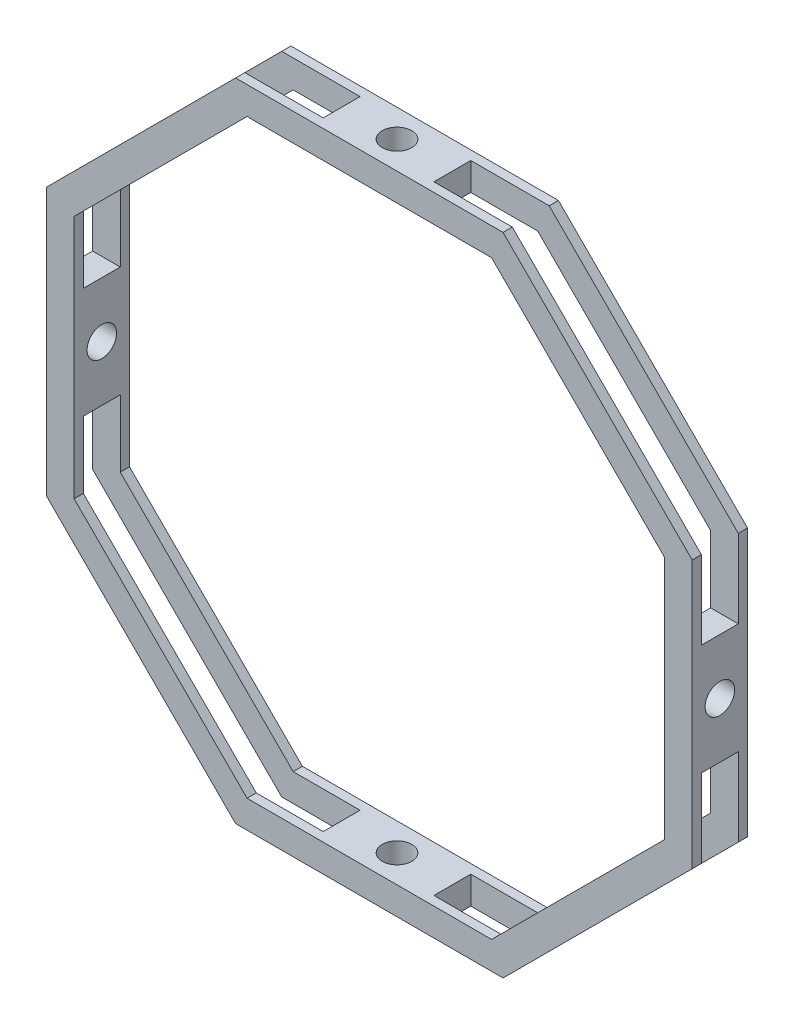
SolidWorks part; units mm, degrees
ref_plane "Plano frontal" through (0, 0, 0) normal (0, 0, 1) x (1, 0, 0)
ref_plane "Plano superior" through (0, 0, 0) normal (0, 1, 0) x (1, 0, 0)
ref_plane "Plano direito" through (0, 0, 0) normal (1, 0, 0) x (0, 0, -1)
sketch "Esboço1" plane through (0, 0, 0) normal (0, 0, 1) x (1, 0, 0)
  line L9 (175, 72.4874) -> (72.4874, 175)
  line L10 (72.4874, 175) -> (-72.4874, 175)
  line L11 (-72.4874, 175) -> (-175, 72.4874)
  line L12 (-175, 72.4874) -> (-175, -72.4874)
  line L13 (-175, -72.4874) -> (-72.4874, -175)
  line L14 (-72.4874, -175) -> (72.4874, -175)
  line L15 (72.4874, -175) -> (175, -72.4874)
  line L16 (175, -72.4874) -> (175, 72.4874)
  line L17 (160, 66.2742) -> (66.2742, 160)
  line L18 (66.2742, 160) -> (-66.2742, 160)
  line L19 (-66.2742, 160) -> (-160, 66.2742)
  line L20 (-160, 66.2742) -> (-160, -66.2742)
  line L21 (-160, -66.2742) -> (-66.2742, -160)
  line L22 (-66.2742, -160) -> (66.2742, -160)
  line L23 (66.2742, -160) -> (160, -66.2742)
  line L24 (160, -66.2742) -> (160, 66.2742)
  circle A0 centre (0, 0) radius 175 construction
  circle A1 centre (0, 0) radius 160 construction
extrude "Ressalto-extrusão1" add sketch "Esboço1" along normal blind 30
sketch "Esboço2" plane through (175, 0, 0) normal (1, 0, 0) x (0, 0, -1)
  line L0 (-30, 72.4874) -> (0, 72.4874) construction
  line L1 (-30, -72.4874) -> (-30, 72.4874) construction
  line L3 (0, 0) -> (0, 30)
  line L4 (0, 30) -> (-30, 30)
  line L5 (-30, 0) -> (-30, 30)
  line L6 (0, 30) -> (-5, 30)
  line L8 (0, 0) -> (0, -30)
  line L9 (0, -30) -> (-30, -30)
  line L10 (-30, 0) -> (-30, -30)
  line L11 (0, 30) -> (0, 72.4874)
  line L12 (0, 72.4874) -> (-5, 72.4874)
  line L13 (-5, 30) -> (-5, 72.4874)
  line L14 (-30, -72.4874) -> (0, -72.4874) construction
  line L15 (-30, 30) -> (-25, 30)
  line L16 (-30, 30) -> (-30, 72.4874)
  line L17 (-30, 72.4874) -> (-25, 72.4874)
  line L18 (-25, 30) -> (-25, 72.4874)
  line L19 (-30, -30) -> (-25, -30)
  line L20 (-30, -30) -> (-30, -72.4874)
  line L21 (-30, -72.4874) -> (-25, -72.4874)
  line L22 (-25, -30) -> (-25, -72.4874)
  line L24 (0, -30) -> (-5, -30)
  line L25 (0, -30) -> (0, -72.4874)
  line L26 (0, -72.4874) -> (-5, -72.4874)
  line L27 (-5, -30) -> (-5, -72.4874)
  line M5 (0, 72.4874) -> (-30, 72.4874)
  line M7 (-30, -72.4874) -> (0, -72.4874)
extrude "Corte-extrusão2" cut sketch "Esboço2" against normal through all both and the other way through all contours L18 L4 L13 M5 region at (175, 51.2437, 15)
sketch "Esboço4" plane through (175, 0, 0) normal (1, 0, 0) x (0, 0, -1)
  circle A0 centre (-15, 0) radius 8
extrude "Corte-extrusão3" cut sketch "Esboço4" against normal through all both and the other way through all
extrude "Corte-extrusão4" cut sketch "Esboço2<4>" against normal through all both and the other way through all contours L27 L9 L22 M7 region at (175, -51.2437, 15)
sketch "Esboço2<4>" plane through (175, 0, 0) normal (1, 0, 0) x (0, 0, -1) same geometry as "Esboço2"
sketch "Esboço15" plane through (-123.7437, 123.7437, 0) normal (-0.7071, 0.7071, 0) x (0, 0, 1)
  line L0 (30, 72.4874) -> (0, 72.4874) construction
  line L1 (5, -72.4874) -> (25, -72.4874)
  line L2 (5, -72.4874) -> (5, 72.4874)
  line L3 (5, 72.4874) -> (25, 72.4874)
  line L4 (25, -72.4874) -> (25, 72.4874)
extrude "Corte-extrusão5" cut sketch "Esboço15" against normal through all both and the other way through all
sketch "Esboço16" plane through (123.7437, 123.7437, 0) normal (0.7071, 0.7071, 0) x (0, 0, -1)
  line L0 (-30, 72.4874) -> (0, 72.4874) construction
  line L1 (-25, -72.4874) -> (-5, -72.4874)
  line L2 (-25, -72.4874) -> (-25, 72.4874)
  line L3 (-25, 72.4874) -> (-5, 72.4874)
  line L4 (-5, -72.4874) -> (-5, 72.4874)
extrude "Corte-extrusão6" cut sketch "Esboço16" against normal through all both and the other way through all
sketch "Esboço18" plane through (0, -175, 0) normal (0, -1, 0) x (1, 0, 0)
  line L1 (-72.4874, 25) -> (72.4874, 25)
  line L2 (-72.4874, 25) -> (-72.4874, 5)
  line L3 (-72.4874, 5) -> (72.4874, 5)
  line L4 (72.4874, 25) -> (72.4874, 5)
ref_plane "Plano2" through (160, -30, 5) normal (1, 0, 0) x (0, 0, -1)
sketch "Esboço21" plane through (0, 175, 0) normal (0, 1, 0) x (1, 0, 0)
  line L0 (-72.4874, -5) -> (72.4874, -5) construction
  line L1 (0, -5) -> (30, -5)
  line L2 (0, -5) -> (0, -25)
  line L3 (0, -25) -> (30, -25)
  line L4 (30, -5) -> (30, -25)
  line L5 (-72.4874, -25) -> (72.4874, -25) construction
  line L7 (0, -5) -> (-30, -5)
  line L8 (0, -5) -> (0, -25)
  line L9 (0, -25) -> (-30, -25)
  line L10 (-30, -5) -> (-30, -25)
sketch "Esboço22" plane through (0, 175, 0) normal (0, 1, 0) x (1, 0, 0)
  line L1 (-30, -5) -> (-72.4874, -5)
  line L2 (-30, -5) -> (-30, -25)
  line L3 (-30, -25) -> (-72.4874, -25)
  line L4 (-72.4874, -5) -> (-72.4874, -25)
  line L5 (30, -5) -> (72.4874, -5)
  line L6 (30, -5) -> (30, -25)
  line L7 (30, -25) -> (72.4874, -25)
  line L8 (72.4874, -5) -> (72.4874, -25)
extrude "Corte-extrusão8" cut sketch "Esboço22" against normal through all both and the other way through all
sketch "Esboço23" plane through (0, 175, 0) normal (0, 1, 0) x (1, 0, 0)
  line L0 (0, -5) -> (0, -25) construction
  circle A0 centre (0, -15) radius 8
extrude "Corte-extrusão9" cut sketch "Esboço23" against normal through all both and the other way through all
